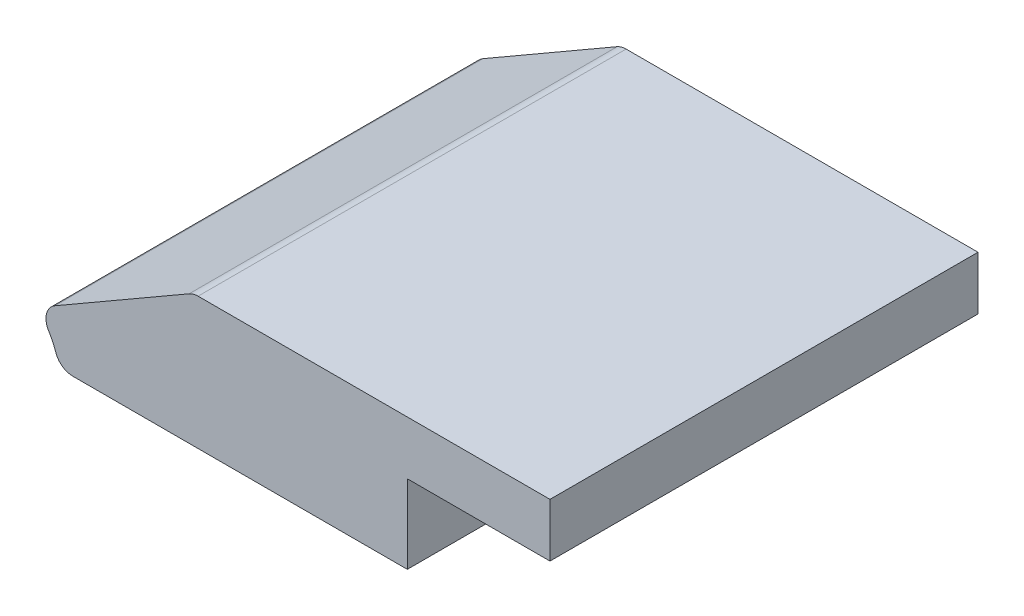
SolidWorks part; units mm, degrees
ref_plane "Front Plane" through (0, 0, 0) normal (0, 0, 1) x (1, 0, 0)
ref_plane "Top Plane" through (0, 0, 0) normal (0, 1, 0) x (1, 0, 0)
ref_plane "Right Plane" through (0, 0, 0) normal (1, 0, 0) x (0, 0, -1)
sketch "Sketch1" plane through (0, 0, 0) normal (0, 0, 1) x (1, 0, 0)
  line L0 (8.6402, 9.3079) -> (36.5125, 25.4)
  line L1 (36.5125, 25.4) -> (100.0125, 25.4)
  line L2 (100.0125, 25.4) -> (100.0125, 15.875)
  line L3 (100.0125, 15.875) -> (74.6125, 15.875)
  line L4 (74.6125, 15.875) -> (74.6125, 1.905)
  line L5 (74.6125, 1.905) -> (12.5563, 1.905)
  arc A0 (12.5563, 1.905) -> (8.6402, 9.3079) centre (0, 0) ccw
  point P9 (12.7, 0)
  point P10 (9.1854, 8.7703)
  point P11 (11.1027, 6.166)
  dimension "D4" = 25.4
  dimension "D1" = 25.4
  dimension "D2" = 13.97
  dimension "D3" = 74.6125
  dimension "D5" = 30
  dimension "D6" = 9.525
  dimension "D7" = 63.5
  dimension "D8" = 15.875
extrude "Boss-Extrude1" add sketch "Sketch1" along normal blind 76.2
fillet "Fillet1" radius 3.175 3 edges at (36.5125, 25.4, 38.1) (12.5563, 1.905, 38.1) (8.6402, 9.3079, 38.1)
